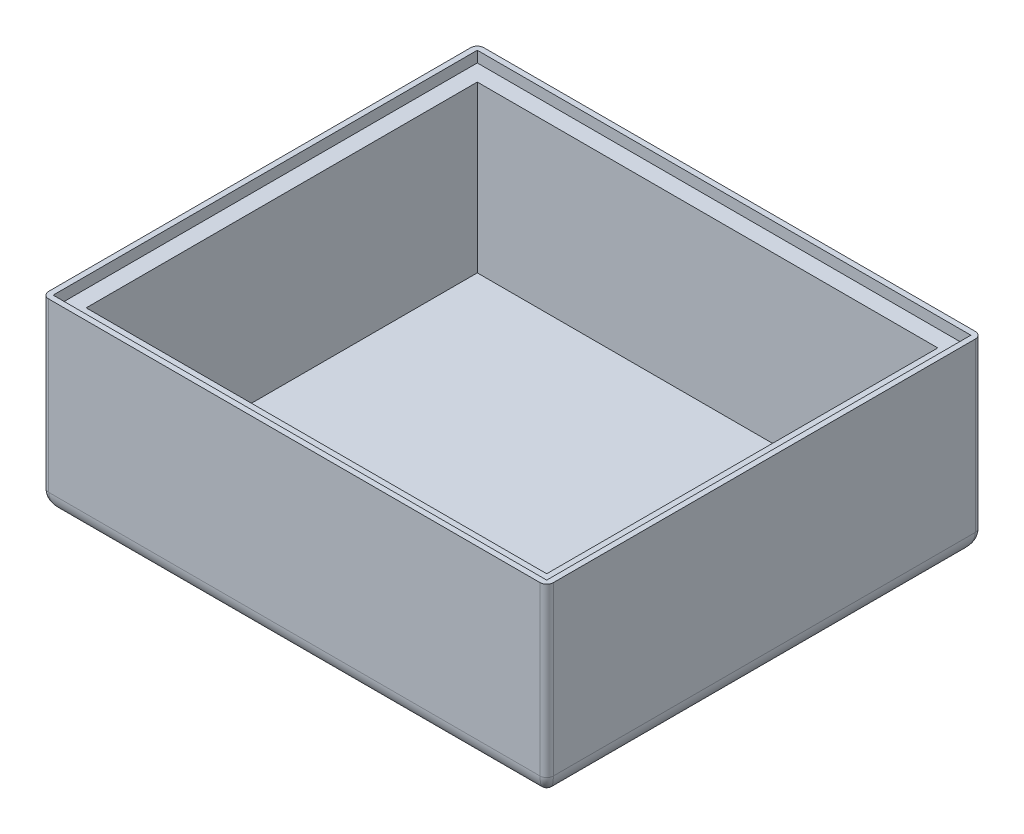
SolidWorks part; units mm, degrees
ref_plane "Front Plane" through (0, 0, 0) normal (0, 0, 1) x (1, 0, 0)
ref_plane "Top Plane" through (0, 0, 0) normal (0, 1, 0) x (1, 0, 0)
ref_plane "Right Plane" through (0, 0, 0) normal (1, 0, 0) x (0, 0, -1)
sketch "Sketch1" plane through (0, 0, 0) normal (0, 1, 0) x (1, 0, 0)
  line L0 (1.27, 23.81) -> (27.81, 23.81)
  line L1 (0, 25.08) -> (29.08, 25.08)
  line L2 (0, 25.08) -> (0, 0)
  line L3 (0, 0) -> (29.08, 0)
  line L4 (29.08, 25.08) -> (29.08, 0)
  line L5 (27.81, 23.81) -> (27.81, 1.27)
  line L6 (1.27, 1.27) -> (27.81, 1.27)
  line L7 (1.27, 23.81) -> (1.27, 1.27)
  dimension "D1" = 29.08
  dimension "D2" = 25.08
  dimension "D3" = 1.27
extrude "Boss-Extrude1" add sketch "Sketch1" along normal blind 0.635 contours L2 L3 L4 L1
extrude "Boss-Extrude2" add sketch "Sketch1<3>" along normal blind 10.16 contours L2 L3 L4 L1 | L7 L6 L5 L0
sketch "Sketch1<3>" plane through (0, 0, 0) normal (0, 1, 0) x (1, 0, 0) same geometry as "Sketch1"
sketch "Sketch7" plane through (0, 10.16, 0) normal (0, 1, 0) x (1, 0, 0)
sketch "Sketch8" plane through (0, 10.16, 0) normal (0, 1, 0) x (1, 0, 0)
  line L4 (0, 25.08) -> (29.08, 25.08)
  line L5 (29.08, 25.08) -> (29.08, 0)
  line L6 (29.08, 0) -> (0, 0)
  line L7 (0, 0) -> (0, 25.08)
  line L8 (28.7625, 24.7625) -> (0.3175, 24.7625)
  line L9 (0.3175, 24.7625) -> (0.3175, 0.3175)
  line L10 (0.3175, 0.3175) -> (28.7625, 0.3175)
  line L11 (28.7625, 0.3175) -> (28.7625, 24.7625)
  line L12 (28.7625, 24.7625) -> (0.3175, 24.7625)
  line L13 (0.3175, 24.7625) -> (0.3175, 0.3175)
  line L14 (0.3175, 0.3175) -> (28.7625, 0.3175)
  line L15 (28.7625, 0.3175) -> (28.7625, 24.7625)
  line L17 (1.27, 23.81) -> (27.81, 23.81)
  line L18 (1.27, 23.81) -> (1.27, 1.27)
  line L19 (1.27, 1.27) -> (27.81, 1.27)
  line L20 (27.81, 23.81) -> (27.81, 1.27)
  dimension "D1" = 0.3175
extrude "Boss-Extrude4" add sketch "Sketch8" along normal blind 0.635 contours L6 L7 L4 L5 | L13 L14 L15 L12
fillet "Fillet3" radius 0.381 4 edges at (0, 5.3975, -25.08) (29.08, 5.3975, -25.08) (0, 5.3975, 0) (29.08, 5.3975, 0)
fillet "Fillet4" radius 1.143 8 edges at (0.1116, 0, -0.1116) (0.1116, 0, -24.9684) (28.9684, 0, -24.9684) (28.9684, 0, -0.1116) (0, 0, -12.54) (14.54, 0, -25.08) (29.08, 0, -12.54) (14.54, 0, 0)
